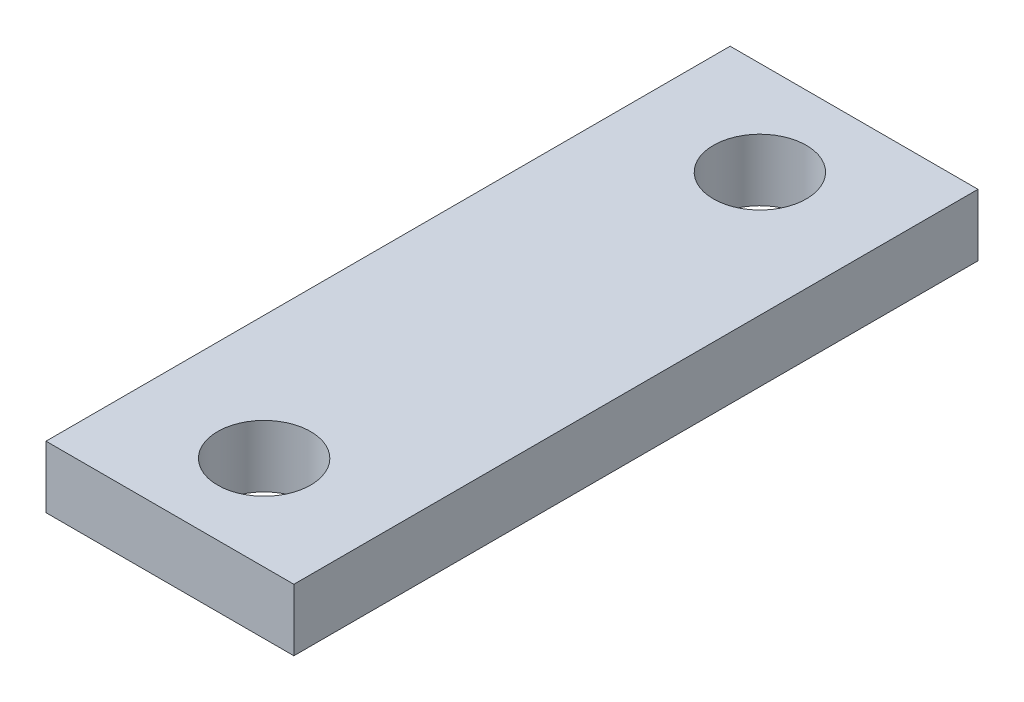
SolidWorks part; units mm, degrees
ref_plane "Front Plane" through (0, 0, 0) normal (0, 0, 1) x (1, 0, 0)
ref_plane "Top Plane" through (0, 0, 0) normal (0, 1, 0) x (1, 0, 0)
ref_plane "Right Plane" through (0, 0, 0) normal (1, 0, 0) x (0, 0, -1)
sketch "Sketch2" plane through (0, 0, 0) normal (0, 1, 0) x (1, 0, 0)
  line L0 (-12.7, 0) -> (12.7, 0) construction
  line L1 (-12.7, 35.052) -> (12.7, 35.052)
  line L2 (-12.7, 35.052) -> (-12.7, -35.052)
  line L3 (-12.7, -35.052) -> (12.7, -35.052)
  line L4 (12.7, 35.052) -> (12.7, -35.052)
  line L5 (0, 25.4) -> (0, -25.4)
  circle A0 centre (0, 25.4) radius 4.7625
  circle A1 centre (0, -25.4) radius 4.7625
  point P10 (0, 0)
  point P11 (0, 0)
  point P12 (0, 0)
  dimension "D3" = 9.525
  dimension "D1" = 25.4
  dimension "D2" = 70.104
  dimension "D4" = 50.8
extrude "Boss-Extrude1" add sketch "Sketch2" along normal blind 6.35 contours L2 L0 A0 L4 L1 | L0 L2 L3 L4 A1 region at (-12.2671, 0, -17.526) region at (-6.35, 0, 0.4329)
equation "\"Lead_Screw_Dist\" = 2in"
equation "\"Lead_Screw_Diam\" = 0.375in"
equation "\"D4@Sketch2\"=\"Lead_Screw_Dist\""
equation "\"D3@Sketch2\"=\"Lead_Screw_Diam\""
